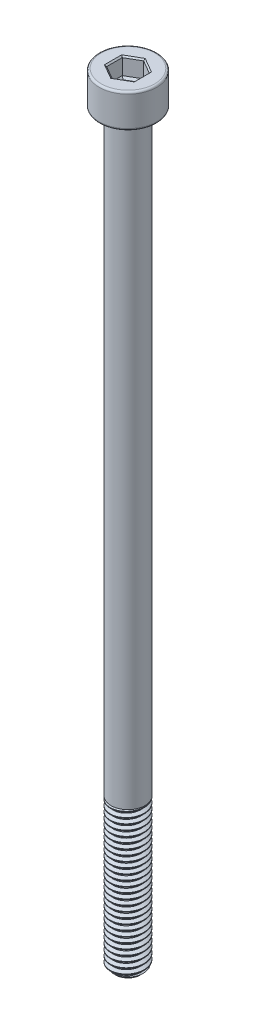
SolidWorks part; units mm, degrees
material "AISI Type A2 Tool Steel"
ref_plane "Front Plane" through (0, 0, 0) normal (0, 0, 1) x (1, 0, 0)
ref_plane "Top Plane" through (0, 0, 0) normal (0, 1, 0) x (1, 0, 0)
ref_plane "Right Plane" through (0, 0, 0) normal (1, 0, 0) x (0, 0, -1)
sketch "Sketch1" plane through (0, 0, 0) normal (0, 1, 0) x (1, 0, 0)
  circle A0 centre (0, 0) radius 2.5
  dimension "D1" = 5
extrude "Boss-Extrude1" add sketch "Sketch1" along normal blind 22
thread "Thread1" pitch 0.8 method cut profile "Thread Profile1" start angle 0, offset 1, length 0, pitch 0.8, diameter 5
ref_plane "Plane1" through (-2.5, 23, 0) normal (0, 0, 1) x (-1, 0, 0)
sketch "Thread Profile1" plane through (-2.5, 23, 0) normal (0, 0, 1) x (-1, 0, 0)
  line L0 (0, 0) -> (0, 0.8) construction
  line L11 (0, 0) -> (0, 0.7)
  line L12 (0, 0.7) -> (-0.433, 0.45)
  line L13 (-0.433, 0.45) -> (-0.433, 0.25)
  line L15 (-0.433, 0.25) -> (0, 0)
  line L17 (-0.433, 0.35) -> (0, 0.35) construction
  point P2 (0, 0)
  dimension "Pitch" = 0.8
  dimension "Profile_Angle" = 60
  dimension "Profile_Land" = 0.2
  dimension "Profile_Height" = 0.433
sketch "Sketch2" plane through (0, 22, 0) normal (0, 1, 0) x (1, 0, 0)
  circle A0 centre (0, 0) radius 2.5
  dimension "D1" = 5
extrude "Boss-Extrude2" add sketch "Sketch2" along normal blind 88
sketch "Sketch3" plane through (0, 110, 0) normal (0, 1, 0) x (1, 0, 0)
  circle A0 centre (0, 0) radius 4.25
  dimension "D1" = 8.5
extrude "Boss-Extrude3" add sketch "Sketch3" along normal blind 5
fillet "Fillet1" radius 0.3 2 edges at (0, 110, 4.25) (0, 115, 4.25)
sketch "Sketch4" plane through (0, 0, 0) normal (0, 0, 1) x (1, 0, 0)
  line L0 (0, 0) -> (0, 0.4416) construction
  line L1 (0, 0) -> (2.51, 0) construction
  line L2 (2.51, 0) -> (2.51, 0.7)
  line L3 (2.51, 0.7) -> (1.81, 0)
  line L4 (1.81, 0) -> (2.51, 0)
  dimension "D1" = 0.7
  dimension "D2" = 45
  dimension "D3" = 2.51
revolve "Cut-Revolve1" cut sketch "Sketch4" angle 360 about L0
sketch "Sketch5" plane through (0, 115, 0) normal (0, 1, 0) x (1, 0, 0)
  line L1 (0, 2.3094) -> (-2, 1.1547)
  line L2 (-2, 1.1547) -> (-2, -1.1547)
  line L3 (-2, -1.1547) -> (0, -2.3094)
  line L4 (0, -2.3094) -> (2, -1.1547)
  line L5 (2, -1.1547) -> (2, 1.1547)
  line L6 (2, 1.1547) -> (0, 2.3094)
  circle A0 centre (0, 0) radius 2 construction
  dimension "D1" = 4
extrude "Cut-Extrude1" cut sketch "Sketch5" against normal blind 2.5
chamfer "Chamfer1" distance 0.2 angle 45 6 edges at (-1, 115, 1.7321) (1, 115, 1.7321) (2, 115, 0) (1, 115, -1.7321) (-1, 115, -1.7321) (-2, 115, 0)
sketch "Sketch6" plane through (0, 112.5, 0) normal (0, 1, 0) x (1, 0, 0)
  line L1 (0, 2.3094) -> (-2, 1.1547)
  line L2 (-2, 1.1547) -> (-2, -1.1547)
  line L3 (-2, -1.1547) -> (0, -2.3094)
  line L4 (0, -2.3094) -> (2, -1.1547)
  line L5 (2, -1.1547) -> (2, 1.1547)
  line L6 (2, 1.1547) -> (0, 2.3094)
  circle A0 centre (0, 0) radius 2 construction
extrude "Cut-Extrude2" cut sketch "Sketch6" against normal blind 0.3 draft 45
